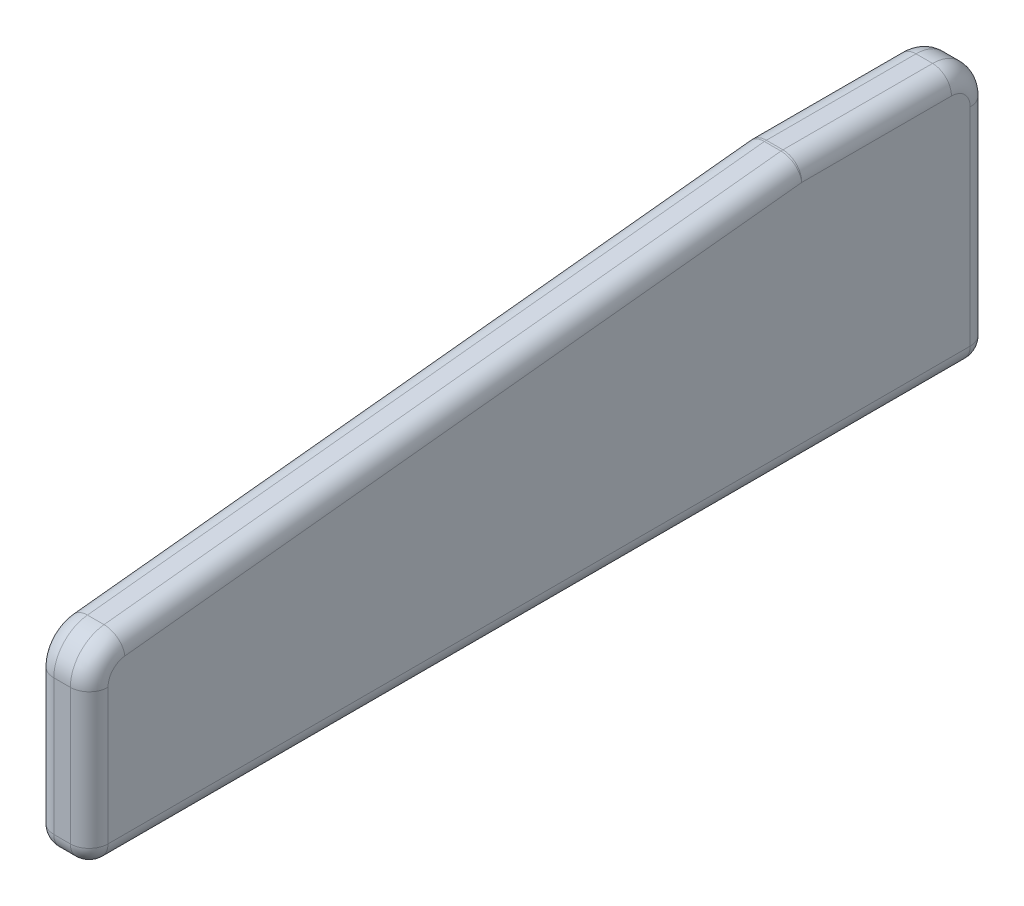
SolidWorks part; units mm, degrees
material "Mahogany"
ref_plane "Front Plane" through (0, 0, 0) normal (0, 0, 1) x (1, 0, 0)
ref_plane "Top Plane" through (0, 0, 0) normal (0, 1, 0) x (1, 0, 0)
ref_plane "Right Plane" through (0, 0, 0) normal (1, 0, 0) x (0, 0, -1)
sketch "Sketch1" plane through (0, 0, 0) normal (1, 0, 0) x (0, 0, -1)
  line L0 (0, 0) -> (0, 84.1309) construction
  line L1 (0, 0) -> (161.7203, 0) construction
  line L2 (-166.9735, -57.6462) -> (123.786, -57.6462)
  line L3 (130.136, -51.2962) -> (130.136, 18.5538)
  line L4 (117.436, 31.2538) -> (66.9711, 31.2538)
  line L5 (66.3027, 31.2185) -> (-161.9603, 7.0566)
  line L6 (-173.3235, -5.5729) -> (-173.3235, -51.2962)
  arc A0 (66.3027, 31.2185) -> (66.9711, 31.2538) centre (66.9711, 24.9038) cw
  arc A1 (117.436, 31.2538) -> (130.136, 18.5538) centre (117.436, 18.5538) cw
  arc A2 (130.136, -51.2962) -> (123.786, -57.6462) centre (123.786, -51.2962) cw
  arc A3 (-166.9735, -57.6462) -> (-173.3235, -51.2962) centre (-166.9735, -51.2962) cw
  arc A4 (-173.3235, -5.5729) -> (-161.9603, 7.0566) centre (-160.6235, -5.5729) cw
  point P11 (66.636, 31.2538)
  point P14 (130.136, 31.2538)
  point P17 (130.136, -57.6462)
  point P20 (-173.3235, -57.6462)
  point P23 (-173.3235, 5.8538)
  dimension "D5" = 6.35
  dimension "D6" = 12.7
  dimension "D7" = 12.7
  dimension "D1" = 241.3
  dimension "D2" = 63.5
  dimension "D3" = 88.9
  dimension "D4" = 63.5
extrude "Boss-Extrude1" add sketch "Sketch1" along normal blind 18.288
fillet "Fillet1" radius 6.35 20 edges at (0, 27.534, -126.4162) (0, -16.3712, -130.136) (0, -55.7864, -128.2761) (0, -57.6462, 21.5938) (0, -55.7864, 171.4636) (0, -28.4346, 173.3235) (0, 2.9216, 170.0646) (0, 19.1375, 47.8288) (0, 31.2449, -66.6364) (18.288, 31.2449, -66.6364) (18.288, 31.2538, -92.2035) (18.288, 27.534, -126.4162) (18.288, -16.3712, -130.136) (18.288, -55.7864, -128.2761) (18.288, -57.6462, 21.5938) (18.288, -55.7864, 171.4636) (18.288, -28.4346, 173.3235) (18.288, 2.9216, 170.0646) (0, 31.2538, -92.2035) (18.288, 19.1375, 47.8288)
